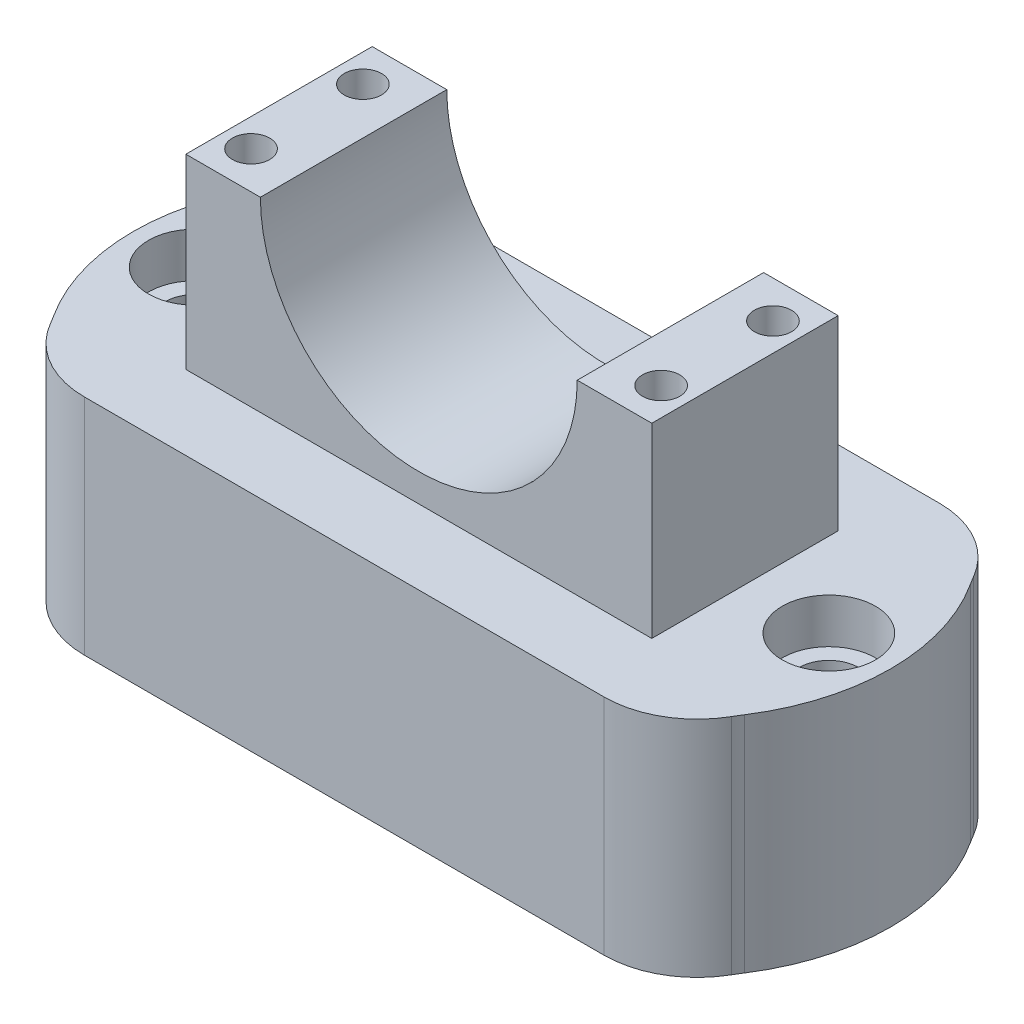
SolidWorks part; units mm, degrees
ref_plane "Alzado" through (0, 0, 0) normal (0, 0, 1) x (1, 0, 0)
ref_plane "Planta" through (0, 0, 0) normal (0, 1, 0) x (1, 0, 0)
ref_plane "Vista lateral" through (0, 0, 0) normal (1, 0, 0) x (0, 0, -1)
sketch "Croquis2" plane through (0, 0, 0) normal (0, 1, 0) x (1, 0, 0)
  line L0 (0, 0) -> (34, 0) construction
  line L1 (17, 9) -> (17, -9) construction
  line L2 (40.6, 0) -> (-6.6, 0) construction
  line L3 (-6.6, -9) -> (-6.6, 9)
  line L4 (-6.6, 9) -> (40.6, 9)
  line L5 (40.6, 9) -> (40.6, -9)
  line L6 (40.6, -9) -> (-6.6, -9)
  line L7 (-6.6, -9) -> (2.7434, -8.9719)
  point P5 (-4.2, 0)
  point P8 (17, 0)
  point P11 (17, 0)
  point P14 (-6.6, 0)
  dimension "D3" = 18
  dimension "D4" = 2.4
extrude "Saliente-Extruir1" add sketch "Croquis2" along normal blind 12 contours L6 L5 L4 L3 region at (17, 0, 0)
sketch "Croquis3" plane through (0, 0, 9) normal (0, 0, 1) x (1, 0, 0)
  line L0 (40.6, 12) -> (-6.6, 12) construction
  line L1 (17, 12) -> (17, 22) construction
  line L2 (17, 22) -> (8.5, 22) construction
  line L3 (8.5, 22) -> (25.5, 22) construction
  line L4 (8.5, 22) -> (4.5, 22)
  line L5 (4.5, 22) -> (4.5, 12)
  line L6 (25.5, 22) -> (29.5, 22)
  line L7 (29.5, 22) -> (29.5, 12)
  line L8 (4.5, 12) -> (29.5, 12)
  line L9 (29.5, 12) -> (29.4278, 11.8928)
  arc A0 (8.5, 22) -> (25.5, 22) centre (17, 22) ccw
  point P6 (17, 12)
  dimension "D1" = 17
  dimension "D2" = 4
  dimension "D3" = 4
  dimension "D4" = 10
ref_plane "Plano1" through (0, 0, 0) normal (0, 0, -1) x (-1, 0, 0)
sketch "Croquis4" plane through (0, 0, 0) normal (0, 0, -1) x (-1, 0, 0)
  line L0 (-25.5, 22) -> (-29.5, 22) construction
  line L1 (-8.5, 22) -> (-4.5, 22) construction
  line L2 (-4.5, 22) -> (-4.5, 12) construction
  line L3 (-29.5, 22) -> (-29.5, 12) construction
  line L4 (-25.5, 22) -> (-29.5, 22)
  line L5 (-8.5, 22) -> (-4.5, 22)
  line L6 (-4.5, 22) -> (-4.5, 12)
  line L7 (-29.5, 22) -> (-29.5, 12)
  line L8 (-4.5, 12) -> (-29.5, 12) construction
  line L9 (-4.5, 12) -> (-29.5, 12)
  arc A0 (-25.5, 22) -> (-8.5, 22) centre (-17, 22) ccw construction
  arc A1 (-25.5, 22) -> (-8.5, 22) centre (-17, 22) ccw
extrude "Saliente-Extruir2" add sketch "Croquis4" along normal blind 5 and the other way blind 5 contours A1 L4 L7 L9 | A1 L9 L6 L5 region at (17, 13.2307, 0)
sketch "Croquis5" plane through (0, 12, 0) normal (0, 1, 0) x (1, 0, 0)
  line L0 (40.6, 0) -> (-6.6, 0) construction
  line L1 (40.6, 9) -> (40.6, -9) construction
  line L2 (-6.6, -9) -> (-6.6, 9) construction
  point P6 (34, 0)
  point P7 (0, 0)
  point P8 (17, 0)
  dimension "D1" = 17
  dimension "D2" = 17
hole_wizard "Refrentado para tornillo con cabeza troncocónica de M31" positions "Croquis3D3" profile "Croquis10" counterbore size "M3" standard "Ansi Metric"
sketch3d "Croquis3D3"
  point P0 (0, 12, 0)
  point P3 (34, 12, 0)
sketch "Croquis10" plane through (0, 12, 0) normal (1, 0, 0) x (0, 0, 1)
  line L0 (0, 0) -> (0, 30.9614)
  line L1 (0, 30.9614) -> (1.6, 30)
  line L2 (1.6, 30) -> (1.6, 2.4)
  line L3 (1.6, 2.4) -> (2.5, 2.4)
  line L4 (2.5, 2.4) -> (2.5, 0)
  line L5 (2.5, 0) -> (0, 0)
  line L10 (0, 30.9614) -> (-1.6, 30) construction
  line L11 (0, -6.35) -> (0, 107.95) construction
  dimension "Diámetro de taladro" = 3.2
  dimension "Profundidad de taladro" = 30
  dimension "Diámetro de refrentado" = 5
  dimension "Profundidad de refrentado" = 2.4
  dimension "Ángulo de perforador" = 118
sketch "Croquis12" plane through (0, 22, 0) normal (0, 1, 0) x (1, 0, 0)
  line L0 (8.5, 0) -> (25.5, 0) construction
  line L4 (8.5, 5) -> (4.5, 5) construction
  line L5 (6, 5) -> (6, -5) construction
  line L6 (8.5, -5) -> (4.5, -5) construction
  line L7 (4.5, -5) -> (4.5, 5) construction
  line L8 (8.5, -5) -> (8.5, 5) construction
  line L9 (25.5, -5) -> (25.5, 5) construction
  line L10 (17, 0) -> (17, 5)
  point P0 (6, 3)
  point P10 (6, -3)
  point P11 (6, 0)
  point P20 (28, 3)
  point P21 (28, -3)
  dimension "D1" = 1.5
  dimension "D2" = 3
  dimension "D3" = 3
hole_wizard "Taladro de margen para M21" positions "Croquis3D4" profile "Croquis13" hole size "M2" standard "Ansi Metric"
sketch3d "Croquis3D4"
  point P0 (6, 22, -3)
  point P3 (6, 22, 3)
  point P6 (28, 22, -3)
  point P9 (28, 22, 3)
sketch "Croquis13" plane through (6, 22, -3) normal (1, 0, 0) x (0, 0, 1)
  line L0 (0, 0) -> (0, 15.6009)
  line L1 (0, 15.6009) -> (1, 15)
  line L2 (1, 15) -> (1, 0)
  line L5 (1, 0) -> (0, 0)
  line L10 (0, 15.6009) -> (-1, 15) construction
  line L11 (0, -6.35) -> (0, 107.95) construction
  dimension "Diámetro de taladro" = 2
  dimension "Profundidad de taladro" = 15
  dimension "Ángulo de perforador" = 118
sketch "Croquis14" plane through (0, 12, 0) normal (0, 1, 0) x (1, 0, 0)
  line L0 (-6.6, 0) -> (45.6974, 0) construction
  line L1 (-6.6, -9) -> (-6.6, 9) construction
  line L2 (17, -9) -> (17, 12.2984) construction
  line L3 (40.6, -9) -> (-6.6, -9) construction
  circle A0 centre (43.9369, 11.4773) radius 10
  circle A1 centre (-9.9369, 11.4773) radius 10
  circle A2 centre (43.9369, -11.4773) radius 10
  circle A3 centre (-9.9369, -11.4773) radius 10
  dimension "D1" = 20
extrude "Cortar-Extruir1" cut sketch "Croquis14" against normal blind 16
fillet "Redondeo1" radius 6 4 edges at (-6.6, 6, -2.0505) (-6.6, 6, 2.0505) (40.6, 6, -2.0505) (40.6, 6, 2.0505)
sketch "Croquis15" plane through (0, 12, 0) normal (0, 1, 0) x (1, 0, 0)
  line L0 (0, 0) -> (7.8428, 0) construction
  line L1 (17, -9) -> (17, 5.6376) construction
  line L2 (34.2487, -9) -> (-0.2487, -9) construction
  arc A0 (-1.5354, 6.0539) -> (-1.5354, -6.0539) centre (7.8428, 0) ccw
  arc A1 (-0.2487, -9) -> (-4.1014, -3.3566) centre (-9.9369, -11.4773) ccw construction
  arc A2 (-6.4054, 0) -> (-4.1014, -3.3566) centre (-0.6, 1.5158) ccw construction
  arc A3 (-4.1014, 3.3566) -> (-6.4054, 0) centre (-0.6, -1.5158) ccw construction
  arc A4 (-4.1014, 3.3566) -> (-0.2487, 9) centre (-9.9369, 11.4773) ccw construction
  arc A5 (-1.5354, -6.0539) -> (-4.1014, -3.3566) centre (-9.9369, -11.4773) ccw
  arc A6 (-6.4054, 0) -> (-4.1014, -3.3566) centre (-0.6, 1.5158) ccw
  arc A7 (-4.1014, 3.3566) -> (-6.4054, 0) centre (-0.6, -1.5158) ccw
  arc A8 (-4.1014, 3.3566) -> (-1.5354, 6.0539) centre (-9.9369, 11.4773) ccw
  arc A9 (38.1014, 3.3566) -> (35.5354, 6.0539) centre (43.9369, 11.4773) cw
  arc A10 (38.1014, 3.3566) -> (40.4054, 0) centre (34.6, -1.5158) cw
  arc A11 (40.4054, 0) -> (38.1014, -3.3566) centre (34.6, 1.5158) cw
  arc A12 (35.5354, -6.0539) -> (38.1014, -3.3566) centre (43.9369, -11.4773) cw
  arc A13 (35.5354, 6.0539) -> (35.5354, -6.0539) centre (26.1572, 0) cw
extrude "Cortar-Extruir2" cut sketch "Croquis15" against normal blind 16
fillet "Redondeo2" radius 5 2 edges at (-0.2487, 6, -9) (34.2487, 6, -9)
fillet "Redondeo3" radius 5 2 edges at (-0.2487, 6, 9) (34.2487, 6, 9)
